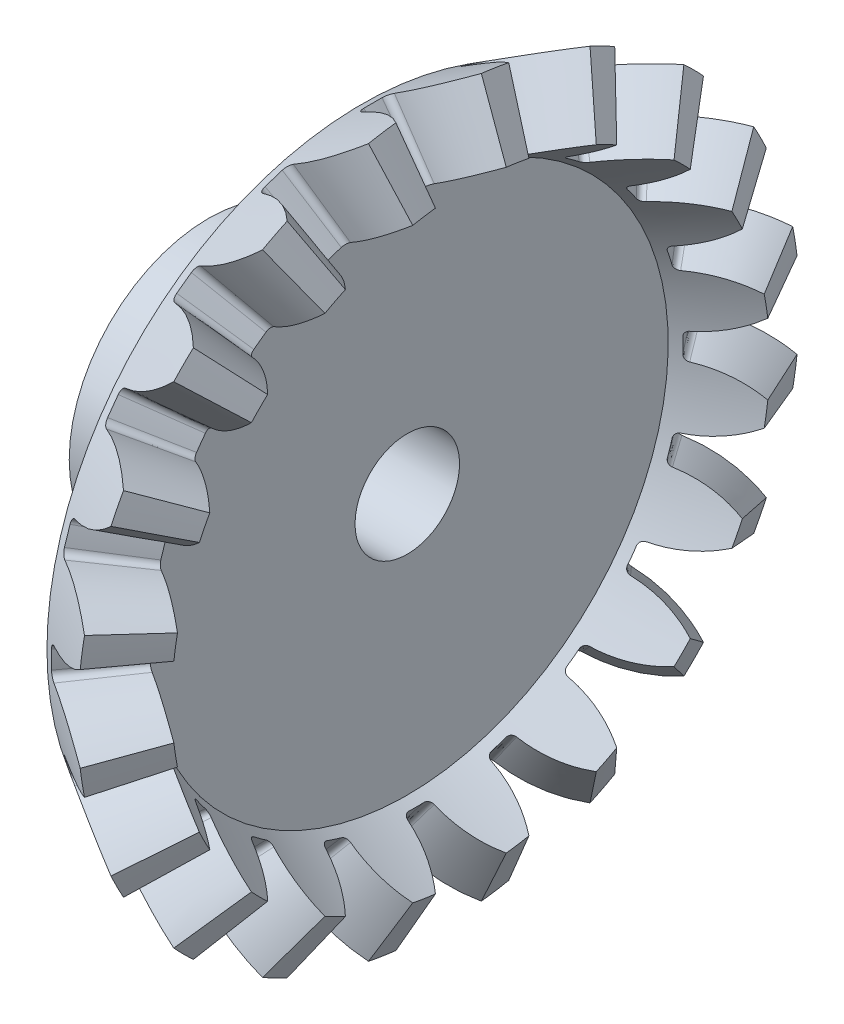
SolidWorks part; units mm, degrees
revolve "Base-Revolve" add sketch "BasProSke" angle 360 about L0 other way angle 9
sketch "BasProSke" plane through (0, 0, 0) normal (0, 1, 0) x (1, 0, 0)
  line L0 (-10, 0) -> (60, 0) construction
  line L1 (0, 0) -> (0, 57.4135)
  line L2 (0, 0) -> (8.2738, 0)
  line L3 (8.2738, 0) -> (8.2738, 47.5672)
  line L4 (48.2442, 0) -> (-6.1702, 90.6907) construction
  line L5 (0, 57.4135) -> (13.9862, 65.8052)
  line L6 (48.2442, 0) -> (-11.1603, 114.1085) construction
  line L7 (48.2442, 0) -> (0, 57.4135) construction
  line L8 (13.9862, 65.8052) -> (19.8614, 54.5197)
  line L9 (19.8614, 54.5197) -> (8.2738, 47.5672)
  line L10 (10.1442, 63.5) -> (-1.8402, 63.5) construction
  dimension "D1" = 114.827
  dimension "D2" = 48.2442
  dimension "D3" = 74.0531
  dimension "D4" = 3.462
ref_plane "Plane1" through (0, 0, 0) normal (0, 0, 1) x (1, 0, 0)
ref_plane "Plane2" through (0, 0, 0) normal (0, 1, 0) x (1, 0, 0)
ref_plane "Plane3" through (0, 0, 0) normal (1, 0, 0) x (0, 0, -1)
sketch "HoldingSke" plane through (0, 0, 0) normal (0, 1, 0) x (1, 0, 0)
  line L0 (0, 0) -> (92.8162, -41.3244)
  line L1 (-15, 0) -> (100, 0) construction
  line L2 (0, 0) -> (-82.0105, 7.681)
  line L3 (0, 0) -> (-11.863, 4.5341)
  line L4 (0, 0) -> (8.1152, 2.9537)
  line L5 (0, 0) -> (-71.3958, -26.6285)
  line L6 (0, 0) -> (-10.5278, -7.1032)
  line L7 (-82.0105, 7.681) -> (-81.4384, 83.8789)
  line L8 (-76.2, 54.61) -> (-54.61, 54.61)
  line L9 (-71.009, 38.7566) -> (-53.1078, 45.2721)
  line L10 (-76.2, 71.12) -> (104.1128, 71.12)
  line L11 (0, 0) -> (-12.7, 0)
  line L12 (-76.2, 101.6) -> (-75.9714, 101.6)
  line L13 (24.9733, 27.94) -> (52.954, 28.2846)
  line L14 (24.9733, 27.94) -> (25.0241, 27.9398)
  line L15 (24.9733, 27.94) -> (100.3933, 29.8918)
  line L16 (-82.0105, 7.681) -> (44.2755, -19.1619)
  circle A0 centre (0, 0) radius 9.525
  circle A1 centre (0, 0) radius 25.4
  circle A2 centre (0, 0) radius 25.4
  circle A3 centre (0, 0) radius 9.525
  dimension "Num_teeth" = 20
  dimension "Pitch_radius" = 180.3128
  dimension "Width" = 12.7
ref_plane "ToothPln" through (6.9931, 61.6094, 0) normal (-0.5145, 0.8575, 0) x (0, 0, -1)
ref_plane "ToothPln2" through (12.7705, -21.2842, 0) normal (-0.5145, 0.8575, 0) x (0, 0, 1)
sketch "TooCutSke" plane through (6.9931, 61.6094, 0) normal (-0.5145, 0.8575, 0) x (0, 0, -1)
  line L2 (0, 59.8253) -> (274.7086, -1674.6166) construction
  line L3 (0, 59.8253) -> (146.9816, -1765.6112) construction
  line L4 (0, -15.621) -> (0, 105.791) construction
  line L6 (-24.765, -8.1553) -> (21.082, -8.1553) construction
  line L7 (9.9336, -2.893) -> (5.0814, -3.2836) construction
  arc A0 (-8.6464, -8.9737) -> (8.6464, -8.9737) centre (0, 59.8253) ccw
  arc A1 (-1.6508, 5.8145) -> (1.6508, 5.8145) centre (0, 59.8253) ccw
  circle A2 centre (0, 59.8253) radius 63.5 construction
  circle A3 centre (0, 59.8253) radius 59.6705 construction
  arc A4 (2.9271, 4.6951) -> (1.6508, 5.8145) centre (1.6888, 4.5705) ccw
  arc A5 (2.9271, 4.6951) -> (8.6464, -8.9737) centre (28.1995, 7.2386) ccw
  arc A6 (-8.6464, -8.9737) -> (-2.9271, 4.6951) centre (-28.1995, 7.2386) ccw
  arc A7 (-1.6508, 5.8145) -> (-2.9271, 4.6951) centre (-1.6888, 4.5705) ccw
  ellipse E0 centre (0, 25.7012) end of major axis (65.8052, 25.7012) minor radius 33.8565 construction
sketch "TooCutSke2" plane through (12.7705, -21.2842, 0) normal (-0.5145, 0.8575, 0) x (0, 0, 1)
  line L0 (0, 0) -> (0, 68.072) construction
  line L2 (21.082, 29.539) -> (-20.32, 29.539) construction
  circle A0 centre (0, 41.369) radius 0.0127
  ellipse E1 centre (0, 0) end of major axis (-57.4135, 0) minor radius 29.539 construction
loft "ToothCut" cut profiles "TooCutSke2", "TooCutSke"
pattern_circular "TeethCuts" count 20 every 18 about axis through (-10, 0, 0) along (1, 0, 0) of "ToothCut"
sketch "HubSke" plane through (0, 0, 0) normal (-1, 0, 0) x (0, 0, 1)
  circle A0 centre (0, 0) radius 25.4
  dimension "Diameter" = 50.8
extrude "Hub" add sketch "HubSke" along normal blind 27.9559
sketch "BorSke" plane through (0, 0, 0) normal (1, 0, 0) x (0, 0, -1)
  circle A0 centre (0, 0) radius 9.525
  dimension "Diameter" = 19.05
extrude "Bore" cut sketch "BorSke" along normal mid plane 152.4001
sketch "KeySke" plane through (0, 0, 0) normal (1, 0, 0) x (0, 0, -1)
  line L0 (-3.175, 0) -> (-3.175, 12.065)
  line L1 (-3.175, 12.065) -> (3.175, 12.065)
  line L2 (3.175, 12.065) -> (3.175, 0)
  line L3 (0, 0) -> (0, 34) construction
  line L4 (-3.175, 0) -> (3.175, 0)
  dimension "Offset" = 12.065
extrude "Keyway" [suppressed] cut sketch "KeySke" along normal mid plane 152.4001
pattern_circular "Keyway2" [suppressed] count 2 every 90 about axis through (-10, 0, 0) along (1, 0, 0) reverse direction yes
equation "' \"Pitch@HoldingSke\" = 4"
equation "' \"Num_teeth@HoldingSke\" = 20"
equation "' \"Mating_teeth@HoldingSke\" = 12"
equation "' \"Ap@HoldingSke\" =  20"
equation "' \"Ap@HoldingSke\" = 20"
equation "' \"Width@HoldingSke\" = 0.5"
equation "' \"Hub_dia@HoldingSke\"= 2"
equation "' \"Hub_dia@HoldingSke\" = 2"
equation "' \"Mounting_dist@HoldingSke\" = 3"
equation "' \"Bore@HoldingSke\" = 0.75"
equation "' \"T_dim@HoldingSke\" = 0.85"
equation "' \"Width@KeySke\" = 0.25"
equation "' \"Show_teeth@HoldingSke\" = 100"
equation "' \"Backlash@HoldingSke\" = 0.009"
equation "' \"Addendum_fac@HoldingSke\" = 1.0"
equation "' \"Dedendum_fac@HoldingSke\" = 1.188"
equation "' \"Dedendum_add@HoldingSke\" = 0.002"
equation "' \"Clearance_fac@HoldingSke\" = 0.188"
equation " \"Addendum_fac@HoldingSke\" = 0.54 + 0.46 / (\"Num_teeth@HoldingSke\" /  \"Mating_teeth@HoldingSke\" ) ^ 2"
equation "' \"Addendum_fac@HoldingSke\" = 2 - (0.54 + 0.46 / (\"Mating_teeth@HoldingSke\" /  \"Num_teeth@HoldingSke\" ) ^ 2)"
equation "\"Dedendum_fac@HoldingSke\" = 2.188 - \"Addendum_fac@HoldingSke\""
equation "\"Pitch_rad@BasProSke\" = \"Num_teeth@HoldingSke\" / \"Pitch@HoldingSke\" / 2"
equation "\"Pitch_ang@BasProSke\" = atn(\"Num_teeth@HoldingSke\" / \"Mating_teeth@HoldingSke\") * (180 / 3.14159265)"
equation "\"Addendum@BasProSke\" = \"Addendum_fac@HoldingSke\" / \"Pitch@HoldingSke\""
equation "\"Dedendum_plus@BasProSke\" = (\"Dedendum_fac@HoldingSke\" / \"Pitch@HoldingSke\" + \"Dedendum_add@HoldingSke\") * 1.25"
equation "\"Face_wid@BasProSke\" = \"Width@HoldingSke\""
equation "\"Radius@TooCutSke\" = ((\"Num_teeth@HoldingSke\" + 2 * \"Addendum_fac@HoldingSke\") / \"Pitch@HoldingSke\" ) / 2"
equation "\"Overcut_dia@TooCutSke\" =  1.02 * (\"Num_teeth@HoldingSke\" + 2 * \"Addendum_fac@HoldingSke\") / \"Pitch@HoldingSke\""
equation "\"Pitch_dia@TooCutSke\" = \"Num_teeth@HoldingSke\" / \"Pitch@HoldingSke\""
equation "\"Base_dia@TooCutSke\" = \"Num_teeth@HoldingSke\" / \"Pitch@HoldingSke\" * cos((\"Ap@HoldingSke\"  * 3.14159265 / 180))"
equation "'  \"Root_dia@TooCutSke\" =  (\"Num_teeth@HoldingSke\" + 2) / \"Pitch@HoldingSke\" - 2 * (\"Addendum_fac@HoldingSke\" + \"Dedendum_fac@HoldingSke\") / \"Pitch@HoldingSke\" - \"Dedendum_add@HoldingSke\" * 2"
equation "'  \"Root_dia@TooCutSke\" = (\"Num_teeth@HoldingSke\" + 2) / \"Pitch@HoldingSke\" - 2 * (\"Addendum_fac@HoldingSke\" + \"Dedendum_fac@HoldingSke\") / \"Pitch@HoldingSke\" - \"Dedendum_add@HoldingSke\" * 2"
equation "\"Root_dia@TooCutSke\" =  \"Num_teeth@HoldingSke\" / \"Pitch@HoldingSke\" - 2 * \"Dedendum_fac@HoldingSke\" / \"Pitch@HoldingSke\" - \"Dedendum_add@HoldingSke\" * 2"
equation "\"Half_ang@TooCutSke\" = 180 / \"Num_teeth@HoldingSke\""
equation "\"Half_CT@TooCutSke\" = \"Num_teeth@HoldingSke\" / \"Pitch@HoldingSke\" * sin((3.14159265 / 2 / \"Num_teeth@HoldingSke\")) / 2 - 2 * \"Backlash@HoldingSke\" / 4"
equation "\"Flank_rad@TooCutSke\" = \"Num_teeth@HoldingSke\" / \"Pitch@HoldingSke\" / 5"
equation "\"Root_fillet@TooCutSke\" = \"Clearance_fac@HoldingSke\" / \"Pitch@HoldingSke\" + \"Dedendum_add@HoldingSke\""
equation "\"Offset@ToothPln2\"  = \"Num_teeth@HoldingSke\" / \"Pitch@HoldingSke\" / 2 / sin(atn(\"Num_teeth@HoldingSke\" / \"Mating_teeth@HoldingSke\"))"
equation "\"Dedendum_plus@TooCutSke2\" = \"Dedendum_plus@BasProSke\""
equation "\"MHD@HoldingSke\" = \"Num_teeth@HoldingSke\" / \"Pitch@HoldingSke\" - 2 * \"Dedendum_plus@BasProSke\" * cos(atn(\"Num_teeth@HoldingSke\" / \"Mating_teeth@HoldingSke\"))"
equation "\"MBD@HoldingSke\" = \"Num_teeth@HoldingSke\" / \"Pitch@HoldingSke\" - 2 * \"Dedendum_plus@BasProSke\" * cos(atn(\"Num_teeth@HoldingSke\" / \"Mating_teeth@HoldingSke\")) - 0.002"
equation "\"MnMD@HoldingSke\" =  \"Num_teeth@HoldingSke\" / \"Pitch@HoldingSke\" / 2 / (\"Num_teeth@HoldingSke\" / \"Mating_teeth@HoldingSke\") + \"Dedendum_plus@BasProSke\" * sin(atn(\"Num_teeth@HoldingSke\" / \"Mating_teeth@HoldingSke\"))"
equation "\"OAL@HoldingSke\" = \"MnMD@HoldingSke\""
equation "\"MHD@HoldingSke\" = ((sgn( \"MHD@HoldingSke\" - \"Hub_dia@HoldingSke\" )-1)*( \"MHD@HoldingSke\" - \"Hub_dia@HoldingSke\" ))/-2+ \"Hub_dia@HoldingSke\""
equation "\"MBD@HoldingSke\" = ((sgn( \"MBD@HoldingSke\" - \"Bore@HoldingSke\" )-1)*( \"MBD@HoldingSke\" - \"Bore@HoldingSke\" ))/-2+ \"Bore@HoldingSke\""
equation "\"Face_wid@BasProSke\" = ((sgn( \"Face_wid@BasProSke\" - \"Offset@ToothPln2\" * 0.9)-1)*( \"Face_wid@BasProSke\" - \"Offset@ToothPln2\" * 0.9))/-2+ \"Offset@ToothPln2\" * 0.9"
equation "\"OAL@HoldingSke\" = ((sgn( \"OAL@HoldingSke\" - \"Mounting_dist@HoldingSke\" )+1)*( \"OAL@HoldingSke\" - \"Mounting_dist@HoldingSke\" ))/2 + \"Mounting_dist@HoldingSke\" + 0.000002"
equation "\"Num_teeth@TeethCuts\" = int( \"Show_teeth@HoldingSke\" ) + 1"
equation "\"Num_teeth@TeethCuts\" = ((sgn( \"Num_teeth@TeethCuts\" - \"Num_teeth@HoldingSke\" )-1)*( \"Num_teeth@TeethCuts\" - \"Num_teeth@HoldingSke\" ))/-2+ \"Num_teeth@HoldingSke\""
equation "\"Num_teeth@TeethCuts\" = ((sgn( \"Num_teeth@TeethCuts\" - 2.0)+1)*( \"Num_teeth@TeethCuts\" - 2.0))/2 +2.0"
equation "\"Angle@TeethCuts\" = 360.0 / \"Num_teeth@HoldingSke\""
equation "\"Diameter@HubSke\" = \"MHD@HoldingSke\""
equation "\"Length@Hub\" = \"OAL@HoldingSke\" - \"MnMD@HoldingSke\" + 0.000002"
equation "\"Diameter@BorSke\" = \"MBD@HoldingSke\""
equation "\"D1@Bore\" = \"OAL@HoldingSke\" * 2.0"
equation "\"D1@Keyway\" = \"OAL@HoldingSke\" * 2.0"
equation "\"Offset@KeySke\" = \"T_dim@HoldingSke\" - \"MBD@HoldingSke\" / 2.0"
